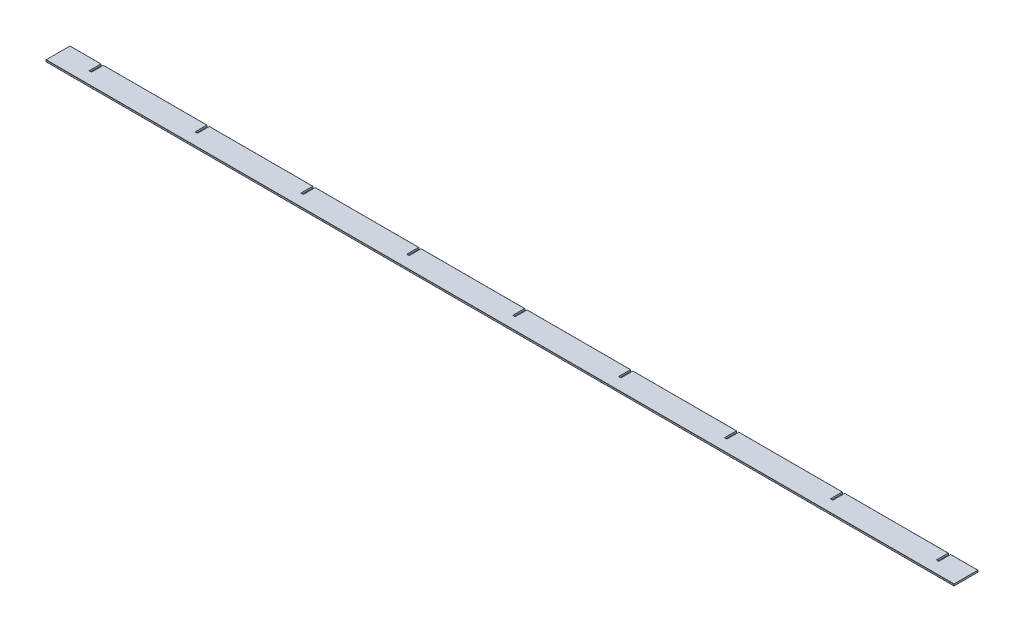
SolidWorks part; units mm, degrees
material "Alloy Steel"
ref_plane "Front Plane" through (0, 0, 0) normal (0, 0, 1) x (1, 0, 0)
ref_plane "Top Plane" through (0, 0, 0) normal (0, 1, 0) x (1, 0, 0)
ref_plane "Right Plane" through (0, 0, 0) normal (1, 0, 0) x (0, 0, -1)
sketch "Sketch1" plane through (0, 0, 0) normal (0, 1, 0) x (1, 0, 0)
  line L1 (-754, -20) -> (754, -20)
  line L2 (-754, -20) -> (-754, 20)
  line L3 (-754, 20) -> (754, 20)
  line L4 (754, -20) -> (754, 20)
  line L5 (-754, -20) -> (754, 20) construction
  line L6 (-754, 20) -> (754, -20) construction
  point P0 (0, 0)
  dimension "D1" = 1508
  dimension "D2" = 40
extrude "Boss-Extrude1" add sketch "Sketch1" along normal blind 1.5 and the other way blind 1.5
fillet "Fillet1" radius 0.35 4 edges at (0, -1.5, -20) (0, -1.5, 20) (0, 1.5, -20) (0, 1.5, 20)
sketch "Sketch2" plane through (0, 1.5, 0) normal (0, 1, 0) x (1, 0, 0)
  line L0 (754, 20) -> (706.83, 20) construction
  line L1 (-754, 20) -> (754, 20) construction
  line L2 (528.92, 0) -> (532.92, 0)
  line L3 (704.83, 20) -> (708.83, 20)
  line L4 (704.83, 20) -> (704.83, 0)
  line L5 (704.83, 0) -> (708.83, 0)
  line L6 (708.83, 20) -> (708.83, 0)
  line L7 (532.92, 20) -> (532.92, 0)
  line L8 (528.92, 20) -> (528.92, 0)
  line L9 (528.92, 20) -> (532.92, 20)
  line L10 (353.01, 0) -> (357.01, 0)
  line L11 (357.01, 20) -> (357.01, 0)
  line L12 (353.01, 20) -> (353.01, 0)
  line L13 (353.01, 20) -> (357.01, 20)
  line L14 (177.1, 0) -> (181.1, 0)
  line L15 (181.1, 20) -> (181.1, 0)
  line L16 (177.1, 20) -> (177.1, 0)
  line L17 (177.1, 20) -> (181.1, 20)
  line L18 (1.19, 0) -> (5.19, 0)
  line L19 (5.19, 20) -> (5.19, 0)
  line L20 (1.19, 20) -> (1.19, 0)
  line L21 (1.19, 20) -> (5.19, 20)
  line L22 (-174.72, 0) -> (-170.72, 0)
  line L23 (-170.72, 20) -> (-170.72, 0)
  line L24 (-174.72, 20) -> (-174.72, 0)
  line L25 (-174.72, 20) -> (-170.72, 20)
  line L26 (-350.63, 0) -> (-346.63, 0)
  line L27 (-346.63, 20) -> (-346.63, 0)
  line L28 (-350.63, 20) -> (-350.63, 0)
  line L29 (-350.63, 20) -> (-346.63, 20)
  line L30 (-526.54, 0) -> (-522.54, 0)
  line L31 (-522.54, 20) -> (-522.54, 0)
  line L32 (-526.54, 20) -> (-526.54, 0)
  line L33 (-526.54, 20) -> (-522.54, 20)
  line L34 (-702.45, 0) -> (-698.45, 0)
  line L35 (-698.45, 20) -> (-698.45, 0)
  line L36 (-702.45, 20) -> (-702.45, 0)
  line L37 (-702.45, 20) -> (-698.45, 20)
  line L38 (704.83, 0) -> (528.92, 0) construction
  dimension "D1" = 47.17
  dimension "D2" = 20
  dimension "D3" = 4
  dimension "D4" = 2
  dimension "D6" = 175.91
  dimension "D5" = 9
extrude "Cut-Extrude1" cut sketch "Sketch2" against normal through all
